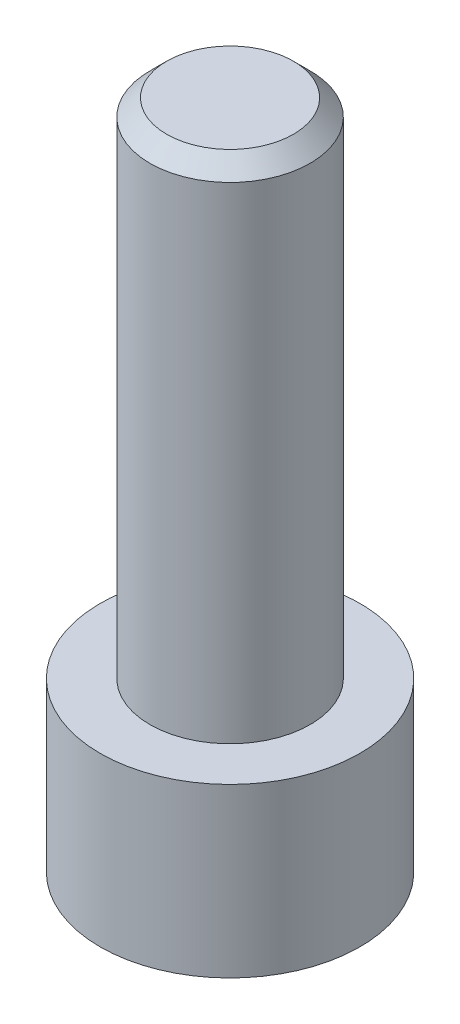
SolidWorks part; units mm, degrees
ref_plane "Front Plane" through (0, 0, 0) normal (0, 0, 1) x (1, 0, 0)
ref_plane "Top Plane" through (0, 0, 0) normal (0, 1, 0) x (1, 0, 0)
ref_plane "Right Plane" through (0, 0, 0) normal (1, 0, 0) x (0, 0, -1)
sketch "Sketch1" plane through (0, 0, 0) normal (0, 1, 0) x (1, 0, 0)
  line L1 (4.4745, 0) -> (2.2372, 3.875) construction
  line L2 (2.2372, 3.875) -> (-2.2372, 3.875) construction
  line L3 (-2.2372, 3.875) -> (-4.4745, 0) construction
  line L4 (-4.4745, 0) -> (-2.2372, -3.875) construction
  line L5 (-2.2372, -3.875) -> (2.2372, -3.875) construction
  line L6 (2.2372, -3.875) -> (4.4745, 0) construction
  circle A0 centre (0, 0) radius 3.875
  dimension "D1" = 7.75
extrude "Boss-Extrude1" add sketch "Sketch1" along normal blind 20
sketch "Sketch2" plane through (0, 20, 0) normal (0, 1, 0) x (1, 0, 0)
  circle A0 centre (0, 0) radius 2.39
  dimension "D1" = 4.78
extrude "Cut-Extrude1" cut sketch "Sketch2" against normal blind 15 flip side to cut
ref_axis "Axis1" through (0, 5, 0) along (0, 1, 0)
chamfer "Chamfer1" distance 0.5 angle 45 1 edges at (0, 20, 2.39)
sketch "Sketch5" plane through (0, 20, 0) normal (0, 1, 0) x (1, 0, 0)
  circle A0 centre (0, 0) radius 2.39
  dimension "D1" = 4.78
curve "Helix/Spiral1" pitch 0.7 height 25 turns 35.7143
ref_plane "Plane1" through (0, 20, 2.39) normal (-0.9989, -0.0466, 0) x (0, 0, 1)
sketch "Sketch8" plane through (0, 0, 0) normal (0, -1, 0) x (1, 0, 0)
  line L1 (2.6443, 0) -> (1.3221, 2.29)
  line L2 (1.3221, 2.29) -> (-1.3221, 2.29)
  line L3 (-1.3221, 2.29) -> (-2.6443, 0)
  line L4 (-2.6443, 0) -> (-1.3221, -2.29)
  line L5 (-1.3221, -2.29) -> (1.3221, -2.29)
  line L6 (1.3221, -2.29) -> (2.6443, 0)
  circle A0 centre (0, 0) radius 2.29 construction
  dimension "D1" = 4.58
extrude "Cut-Extrude2" cut sketch "Sketch8" against normal blind 3.36
